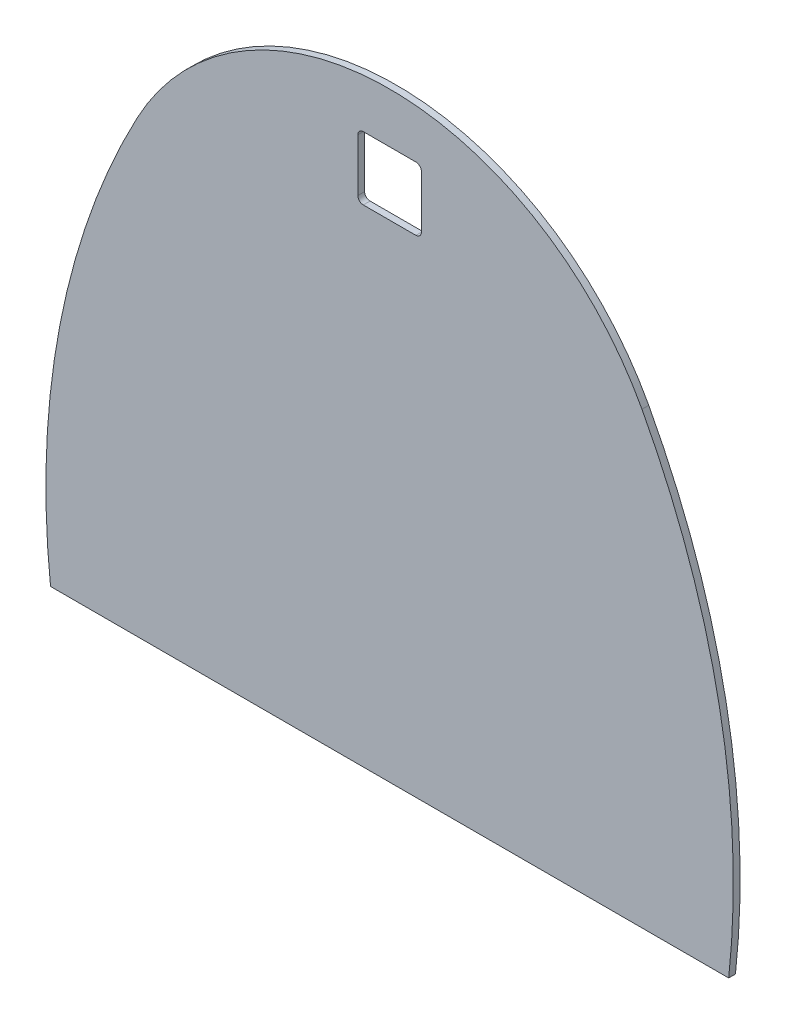
SolidWorks part; units mm, degrees
material "Zoltek Panex 33"
ref_plane "Front Plane" through (0, 0, 0) normal (0, 0, 1) x (1, 0, 0)
ref_plane "Top Plane" through (0, 0, 0) normal (0, 1, 0) x (1, 0, 0)
ref_plane "Right Plane" through (0, 0, 0) normal (1, 0, 0) x (0, 0, -1)
sketch "Sketch1" plane through (0, 0, 0) normal (0, 0, 1) x (1, 0, 0)
  line L8 (-152.4, 0) -> (152.4, 0) construction
  line L9 (-118.1286, 209.55) -> (118.1286, 209.55)
  line L10 (-114.3, 203.2) -> (114.3, 203.2)
  line L14 (-158.7119, -0.6946) -> (158.7119, -0.6946)
  line L21 (-158.7119, -0.6946) -> (-152.4, 0)
  line L22 (152.4, 0) -> (158.7119, -0.6946)
  arc A0 (114.3, 203.2) -> (152.4, 0) centre (-201.0662, 38.897) cw
  arc A1 (-114.3, 203.2) -> (-152.4, 0) centre (201.0662, 38.897) ccw
  arc A2 (-118.1286, 209.55) -> (-158.7119, -0.6946) centre (201.0662, 38.897) ccw
  arc A3 (118.1286, 209.55) -> (158.7119, -0.6946) centre (-201.0662, 38.897) cw
  arc A4 (-119.9315, 206.134) -> (-158.7119, -0.6946) centre (201.0662, 38.897) ccw construction
  arc A5 (119.9315, 206.134) -> (158.7119, -0.6946) centre (-201.0662, 38.897) cw construction
  arc A6 (114.3, 203.2) -> (152.4, 0) centre (-201.0662, 38.897) cw construction
  arc A7 (-114.3, 203.2) -> (-152.4, 0) centre (201.0662, 38.897) ccw construction
  arc A8 (-118.1286, 209.55) -> (118.1286, 209.55) centre (0, 146.3942) cw
  point P0 (0, 0)
  point P13 (0, 203.2)
  dimension "D7" = 304.8
  dimension "D2" = 355.6
  dimension "D3" = 203.2
  dimension "D6" = 228.6
  dimension "D1" = 6.35
  dimension "D4" = 6.35
  dimension "D5" = 6.35
extrude "Boss-Extrude1" add sketch "Sketch1" along normal blind 3.175 contours A8 L9 | L10 A1 L21 L14 L22 A0 | A2 L21 A1 L10 A0 L22 A3 L9 region at (0, 238.6272, 0) region at (0, 96.837, 0)
ref_plane "Plane3" through (160.8838, 0, 0) normal (1, 0, 0) x (0, 0, -1)
sketch "Sketch2" plane through (0, 0, 3.175) normal (0, 0, 1) x (1, 0, 0)
  line L1 (-14.859, 256.8614) -> (14.859, 256.8614)
  line L2 (-14.859, 256.8614) -> (-14.859, 227.1434)
  line L3 (-14.859, 227.1434) -> (14.859, 227.1434)
  line L4 (14.859, 256.8614) -> (14.859, 227.1434)
  line L5 (-14.859, 256.8614) -> (14.859, 227.1434) construction
  line L6 (-14.859, 227.1434) -> (14.859, 256.8614) construction
  point P0 (0, 242.0024)
  dimension "D1" = 29.718
  dimension "D2" = 29.718
  dimension "D3" = 227.838
extrude "Cut-Extrude1" cut sketch "Sketch2" against normal up to next
fillet "Fillet1" radius 2.54 4 edges at (14.859, 227.1434, 1.5875) (14.859, 256.8614, 1.5875) (-14.859, 256.8614, 1.5875) (-14.859, 227.1434, 1.5875)
sketch "Sketch3" plane through (0, 0, 0) normal (0, 0, 1) x (1, 0, 0)
  line L0 (-82.55, 115.9307) -> (82.55, 115.9307) construction
  circle A0 centre (-82.55, 115.9307) radius 41.275
  circle A1 centre (0, 115.9307) radius 41.275
  circle A2 centre (82.55, 115.9307) radius 41.275
  circle A3 centre (-41.275, 187.4211) radius 41.275
  circle A4 centre (41.275, 187.4211) radius 41.275
  circle A5 centre (41.275, 44.4403) radius 41.275
  circle A6 centre (-41.275, 44.4403) radius 41.275
  dimension "D1" = 82.55
